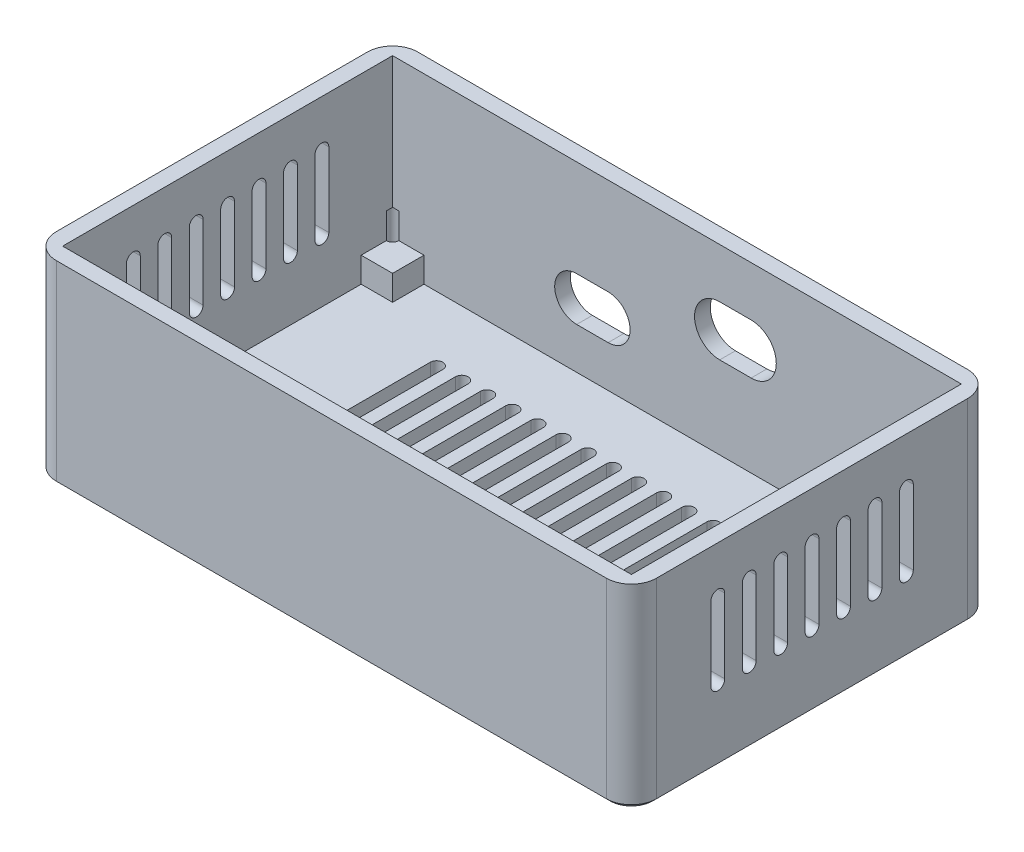
SolidWorks part; units mm, degrees
ref_plane "Front Plane" through (0, 0, 0) normal (0, 0, 1) x (1, 0, 0)
ref_plane "Top Plane" through (0, 0, 0) normal (0, 1, 0) x (1, 0, 0)
ref_plane "Right Plane" through (0, 0, 0) normal (1, 0, 0) x (0, 0, -1)
sketch "Croquis_contorno" plane through (0, 0, 0) normal (0, 1, 0) x (1, 0, 0)
  line L0 (-43.75, -28.75) -> (43.75, -28.75)
  line L1 (47.75, -24.75) -> (47.75, 24.75)
  line L2 (43.75, 28.75) -> (-43.75, 28.75)
  line L3 (-47.75, 24.75) -> (-47.75, -24.75)
  arc A0 (43.75, -28.75) -> (47.75, -24.75) centre (43.75, -24.75) ccw
  arc A1 (47.75, 24.75) -> (43.75, 28.75) centre (43.75, 24.75) ccw
  arc A2 (-43.75, 28.75) -> (-47.75, 24.75) centre (-43.75, 24.75) ccw
  arc A3 (-47.75, -24.75) -> (-43.75, -28.75) centre (-43.75, -24.75) ccw
  dimension "D3" = 4
  dimension "D1" = 95.5
  dimension "D2" = 57.5
extrude "Cuerpo" add sketch "Croquis_contorno" along normal blind 31
ref_plane "Plano_Top Plane_+31" through (0, 31, 0) normal (0, 1, 0) x (1, 0, 0)
sketch "Croquis_hueco_PCB" plane through (0, 31, 0) normal (0, 1, 0) x (1, 0, 0)
  line L1 (-45.25, -26.25) -> (45.25, -26.25)
  line L2 (-45.25, -26.25) -> (-45.25, 26.25)
  line L3 (-45.25, 26.25) -> (45.25, 26.25)
  line L4 (45.25, -26.25) -> (45.25, 26.25)
  line L5 (-45.25, -26.25) -> (45.25, 26.25) construction
  line L6 (-45.25, 26.25) -> (45.25, -26.25) construction
  dimension "D1" = 90.5
  dimension "D2" = 52.5
extrude "Hueco_PCB" cut sketch "Croquis_hueco_PCB" against normal blind 29
ref_plane "Plano_Top Plane_+2" through (0, 2, 0) normal (0, 1, 0) x (1, 0, 0)
sketch "Croquis_apoyos" plane through (0, 2, 0) normal (0, 1, 0) x (1, 0, 0)
  line L0 (45.25, 26.25) -> (-45.25, 26.25) construction
  line L1 (-45.25, -26.25) -> (-40.25, -26.25)
  line L2 (-45.25, -26.25) -> (-45.25, -21.25)
  line L3 (-45.25, -21.25) -> (-40.25, -21.25)
  line L4 (-40.25, -26.25) -> (-40.25, -21.25)
  line L5 (-45.25, -26.25) -> (-40.25, -21.25) construction
  line L6 (-45.25, -21.25) -> (-40.25, -26.25) construction
  line L7 (-45.25, 21.25) -> (-40.25, 21.25)
  line L8 (-45.25, 21.25) -> (-45.25, 26.25)
  line L9 (-45.25, 26.25) -> (-40.25, 26.25)
  line L10 (-40.25, 21.25) -> (-40.25, 26.25)
  line L11 (-45.25, 21.25) -> (-40.25, 26.25) construction
  line L12 (-45.25, 26.25) -> (-40.25, 21.25) construction
  line L13 (45.25, -26.25) -> (45.25, 26.25) construction
  line L14 (40.25, -26.25) -> (45.25, -26.25)
  line L15 (40.25, -26.25) -> (40.25, -21.25)
  line L16 (40.25, -21.25) -> (45.25, -21.25)
  line L17 (45.25, -26.25) -> (45.25, -21.25)
  line L18 (40.25, -26.25) -> (45.25, -21.25) construction
  line L19 (40.25, -21.25) -> (45.25, -26.25) construction
  line L21 (40.25, 21.25) -> (45.25, 21.25)
  line L22 (40.25, 21.25) -> (40.25, 26.25)
  line L23 (40.25, 26.25) -> (45.25, 26.25)
  line L24 (45.25, 21.25) -> (45.25, 26.25)
  line L25 (40.25, 21.25) -> (45.25, 26.25) construction
  line L26 (40.25, 26.25) -> (45.25, 21.25) construction
  point P0 (-42.75, 23.75)
  point P11 (42.75, -23.75)
  point P18 (42.75, 23.75)
  dimension "D1" = 5
  dimension "D2" = 5
extrude "Apoyos_PCB" add sketch "Croquis_apoyos" along normal blind 4
sketch "Croquis_alivios" plane through (0, 2, 0) normal (0, 1, 0) x (1, 0, 0)
  circle A0 centre (-45.25, -26.25) radius 1
  circle A1 centre (-45.25, 26.25) radius 1
  circle A2 centre (45.25, -26.25) radius 1
  circle A3 centre (45.25, 26.25) radius 1
  dimension "D1" = 2
extrude "Alivios_esquinas" cut sketch "Croquis_alivios" along normal blind 8.1
sketch "Croquis_salidas" plane through (0, 0, 0) normal (0, 0, 1) x (1, 0, 0)
  line L0 (6.8, 19.1) -> (11.8, 19.1) construction
  line L1 (6.8, 23.1) -> (11.8, 23.1)
  line L2 (6.8, 15.1) -> (11.8, 15.1)
  line L3 (-15.96, 12.1) -> (-10.96, 12.1) construction
  line L4 (-15.96, 15.6) -> (-10.96, 15.6)
  line L5 (-15.96, 8.6) -> (-10.96, 8.6)
  arc A0 (6.8, 23.1) -> (6.8, 15.1) centre (6.8, 19.1) ccw
  arc A1 (11.8, 15.1) -> (11.8, 23.1) centre (11.8, 19.1) ccw
  arc A2 (-15.96, 15.6) -> (-15.96, 8.6) centre (-15.96, 12.1) ccw
  arc A3 (-10.96, 8.6) -> (-10.96, 15.6) centre (-10.96, 12.1) ccw
  point P2 (9.3, 19.1)
  point P7 (-13.46, 12.1)
  point P14 (0, 0)
extrude "Salidas_USB_y_panel" cut sketch "Croquis_salidas" against normal through all
sketch "Croquis_ventilas" plane through (0, 0, 0) normal (1, 0, 0) x (0, 0, -1)
  line L0 (-15, 11.7) -> (-15, 23.5) construction
  line L1 (-16.1, 11.7) -> (-16.1, 23.5)
  line L2 (-13.9, 11.7) -> (-13.9, 23.5)
  line L3 (-10, 11.7) -> (-10, 23.5) construction
  line L4 (-11.1, 11.7) -> (-11.1, 23.5)
  line L5 (-8.9, 11.7) -> (-8.9, 23.5)
  line L6 (-5, 11.7) -> (-5, 23.5) construction
  line L7 (-6.1, 11.7) -> (-6.1, 23.5)
  line L8 (-3.9, 11.7) -> (-3.9, 23.5)
  line L9 (0, 11.7) -> (0, 23.5) construction
  line L10 (-1.1, 11.7) -> (-1.1, 23.5)
  line L11 (1.1, 11.7) -> (1.1, 23.5)
  line L12 (5, 11.7) -> (5, 23.5) construction
  line L13 (3.9, 11.7) -> (3.9, 23.5)
  line L14 (6.1, 11.7) -> (6.1, 23.5)
  line L15 (10, 11.7) -> (10, 23.5) construction
  line L16 (8.9, 11.7) -> (8.9, 23.5)
  line L17 (11.1, 11.7) -> (11.1, 23.5)
  line L18 (15, 11.7) -> (15, 23.5) construction
  line L19 (13.9, 11.7) -> (13.9, 23.5)
  line L20 (16.1, 11.7) -> (16.1, 23.5)
  arc A0 (-16.1, 11.7) -> (-13.9, 11.7) centre (-15, 11.7) ccw
  arc A1 (-13.9, 23.5) -> (-16.1, 23.5) centre (-15, 23.5) ccw
  arc A2 (-11.1, 11.7) -> (-8.9, 11.7) centre (-10, 11.7) ccw
  arc A3 (-8.9, 23.5) -> (-11.1, 23.5) centre (-10, 23.5) ccw
  arc A4 (-6.1, 11.7) -> (-3.9, 11.7) centre (-5, 11.7) ccw
  arc A5 (-3.9, 23.5) -> (-6.1, 23.5) centre (-5, 23.5) ccw
  arc A6 (-1.1, 11.7) -> (1.1, 11.7) centre (0, 11.7) ccw
  arc A7 (1.1, 23.5) -> (-1.1, 23.5) centre (0, 23.5) ccw
  arc A8 (3.9, 11.7) -> (6.1, 11.7) centre (5, 11.7) ccw
  arc A9 (6.1, 23.5) -> (3.9, 23.5) centre (5, 23.5) ccw
  arc A10 (8.9, 11.7) -> (11.1, 11.7) centre (10, 11.7) ccw
  arc A11 (11.1, 23.5) -> (8.9, 23.5) centre (10, 23.5) ccw
  arc A12 (13.9, 11.7) -> (16.1, 11.7) centre (15, 11.7) ccw
  arc A13 (16.1, 23.5) -> (13.9, 23.5) centre (15, 23.5) ccw
  point P2 (-15, 17.6)
  point P7 (-10, 17.6)
  point P14 (-5, 17.6)
  point P21 (0, 17.6)
  point P29 (5, 17.6)
  point P36 (10, 17.6)
  point P43 (15, 17.6)
  point P50 (0, 0)
extrude "Ventilas_laterales" cut sketch "Croquis_ventilas" along normal through all and the other way through all
sketch "Croquis_rejilla_piso" plane through (0, 0, 0) normal (0, 1, 0) x (1, 0, 0)
  line L0 (-28, -16) -> (-28, 16) construction
  line L1 (-29, -16) -> (-29, 16)
  line L2 (-27, -16) -> (-27, 16)
  line L3 (-24, -16) -> (-24, 16) construction
  line L4 (-25, -16) -> (-25, 16)
  line L5 (-23, -16) -> (-23, 16)
  line L6 (-20, -16) -> (-20, 16) construction
  line L7 (-21, -16) -> (-21, 16)
  line L8 (-19, -16) -> (-19, 16)
  line L9 (-16, -16) -> (-16, 16) construction
  line L10 (-17, -16) -> (-17, 16)
  line L11 (-15, -16) -> (-15, 16)
  line L12 (-12, -16) -> (-12, 16) construction
  line L13 (-13, -16) -> (-13, 16)
  line L14 (-11, -16) -> (-11, 16)
  line L15 (-8, -16) -> (-8, 16) construction
  line L16 (-9, -16) -> (-9, 16)
  line L17 (-7, -16) -> (-7, 16)
  line L18 (-4, -16) -> (-4, 16) construction
  line L19 (-5, -16) -> (-5, 16)
  line L20 (-3, -16) -> (-3, 16)
  line L21 (0, -16) -> (0, 16) construction
  line L22 (-1, -16) -> (-1, 16)
  line L23 (1, -16) -> (1, 16)
  line L24 (4, -16) -> (4, 16) construction
  line L25 (3, -16) -> (3, 16)
  line L26 (5, -16) -> (5, 16)
  line L27 (8, -16) -> (8, 16) construction
  line L28 (7, -16) -> (7, 16)
  line L29 (9, -16) -> (9, 16)
  line L30 (12, -16) -> (12, 16) construction
  line L31 (11, -16) -> (11, 16)
  line L32 (13, -16) -> (13, 16)
  line L33 (16, -16) -> (16, 16) construction
  line L34 (15, -16) -> (15, 16)
  line L35 (17, -16) -> (17, 16)
  line L36 (20, -16) -> (20, 16) construction
  line L37 (19, -16) -> (19, 16)
  line L38 (21, -16) -> (21, 16)
  line L39 (24, -16) -> (24, 16) construction
  line L40 (23, -16) -> (23, 16)
  line L41 (25, -16) -> (25, 16)
  line L42 (28, -16) -> (28, 16) construction
  line L43 (27, -16) -> (27, 16)
  line L44 (29, -16) -> (29, 16)
  arc A0 (-29, -16) -> (-27, -16) centre (-28, -16) ccw
  arc A1 (-27, 16) -> (-29, 16) centre (-28, 16) ccw
  arc A2 (-25, -16) -> (-23, -16) centre (-24, -16) ccw
  arc A3 (-23, 16) -> (-25, 16) centre (-24, 16) ccw
  arc A4 (-21, -16) -> (-19, -16) centre (-20, -16) ccw
  arc A5 (-19, 16) -> (-21, 16) centre (-20, 16) ccw
  arc A6 (-17, -16) -> (-15, -16) centre (-16, -16) ccw
  arc A7 (-15, 16) -> (-17, 16) centre (-16, 16) ccw
  arc A8 (-13, -16) -> (-11, -16) centre (-12, -16) ccw
  arc A9 (-11, 16) -> (-13, 16) centre (-12, 16) ccw
  arc A10 (-9, -16) -> (-7, -16) centre (-8, -16) ccw
  arc A11 (-7, 16) -> (-9, 16) centre (-8, 16) ccw
  arc A12 (-5, -16) -> (-3, -16) centre (-4, -16) ccw
  arc A13 (-3, 16) -> (-5, 16) centre (-4, 16) ccw
  arc A14 (-1, -16) -> (1, -16) centre (0, -16) ccw
  arc A15 (1, 16) -> (-1, 16) centre (0, 16) ccw
  arc A16 (3, -16) -> (5, -16) centre (4, -16) ccw
  arc A17 (5, 16) -> (3, 16) centre (4, 16) ccw
  arc A18 (7, -16) -> (9, -16) centre (8, -16) ccw
  arc A19 (9, 16) -> (7, 16) centre (8, 16) ccw
  arc A20 (11, -16) -> (13, -16) centre (12, -16) ccw
  arc A21 (13, 16) -> (11, 16) centre (12, 16) ccw
  arc A22 (15, -16) -> (17, -16) centre (16, -16) ccw
  arc A23 (17, 16) -> (15, 16) centre (16, 16) ccw
  arc A24 (19, -16) -> (21, -16) centre (20, -16) ccw
  arc A25 (21, 16) -> (19, 16) centre (20, 16) ccw
  arc A26 (23, -16) -> (25, -16) centre (24, -16) ccw
  arc A27 (25, 16) -> (23, 16) centre (24, 16) ccw
  arc A28 (27, -16) -> (29, -16) centre (28, -16) ccw
  arc A29 (29, 16) -> (27, 16) centre (28, 16) ccw
  point P2 (-28, 0)
  point P7 (-24, 0)
  point P14 (-20, 0)
  point P21 (-16, 0)
  point P28 (-12, 0)
  point P35 (-8, 0)
  point P42 (-4, 0)
  point P49 (0, 0)
  point P57 (4, 0)
  point P64 (8, 0)
  point P71 (12, 0)
  point P78 (16, 0)
  point P85 (20, 0)
  point P92 (24, 0)
  point P99 (28, 0)
  point P106 (0, 0)
extrude "Rejilla_piso" cut sketch "Croquis_rejilla_piso" along normal blind 2
chamfer "Chaflan_base" distance 0.6 angle 45 8 edges at (0, 0, 28.75) (46.5784, 0, 27.5784) (47.75, 0, 0) (46.5784, 0, -27.5784) (0, 0, -28.75) (-46.5784, 0, -27.5784) (-47.75, 0, 0) (-46.5784, 0, 27.5784) tangent propagation no
